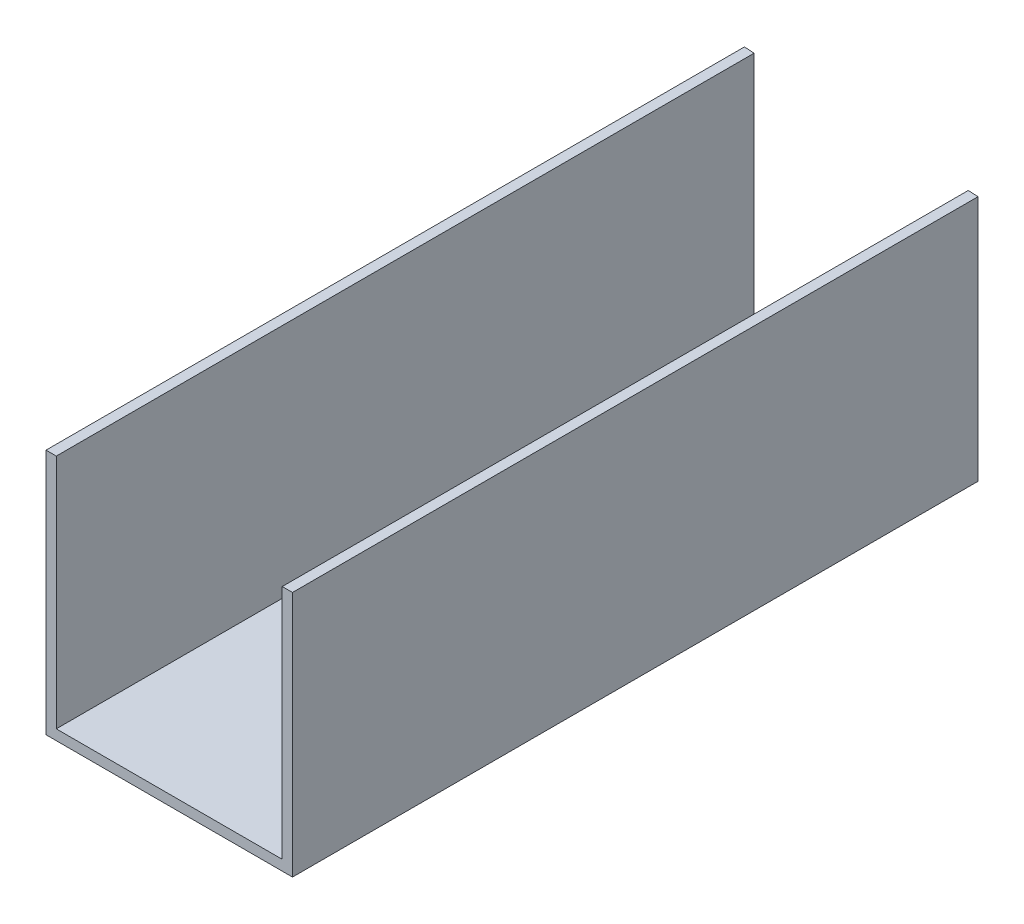
SolidWorks part; units mm, degrees
ref_plane "Front Plane" through (0, 0, 0) normal (0, 0, 1) x (1, 0, 0)
ref_plane "Top Plane" through (0, 0, 0) normal (0, 1, 0) x (1, 0, 0)
ref_plane "Right Plane" through (0, 0, 0) normal (1, 0, 0) x (0, 0, -1)
sketch "Sketch1" plane through (0, 0, 0) normal (0, 0, 1) x (1, 0, 0)
  line L0 (18.3712, 0) -> (-19.7288, 0)
  line L1 (-19.7288, 0) -> (-19.7288, 38.1)
  line L2 (-19.7288, 38.1) -> (-18.1413, 38.1)
  line L3 (-18.1413, 38.1) -> (-18.1413, 1.5875)
  line L4 (-18.1413, 1.5875) -> (16.7837, 1.5875)
  line L5 (16.7837, 1.5875) -> (16.7837, 38.1)
  line L6 (16.7837, 38.1) -> (18.3712, 38.1)
  line L7 (18.3712, 38.1) -> (18.3712, 0)
  dimension "D1" = 1.5875
  dimension "D2" = 1.5875
  dimension "D3" = 1.5875
  dimension "D4" = 38.1
  dimension "D5" = 38.1
  dimension "D6" = 38.1
extrude "Boss-Extrude1" add sketch "Sketch1" along normal blind 107.95
sketch "Sketch2" plane through (0, 38.1, 0) normal (0, 1, 0) x (1, 0, 0)
  line L0 (-19.7288, 0) -> (18.3712, 0)
  line L1 (18.3712, 0) -> (18.3712, -1.9967)
  line L2 (18.3712, -107.95) -> (18.3712, 0) construction
  line L3 (18.3712, -1.9967) -> (-19.7288, 0)
  dimension "D1" = 3
extrude "Cut-Extrude1" cut sketch "Sketch2" against normal blind 98.425
